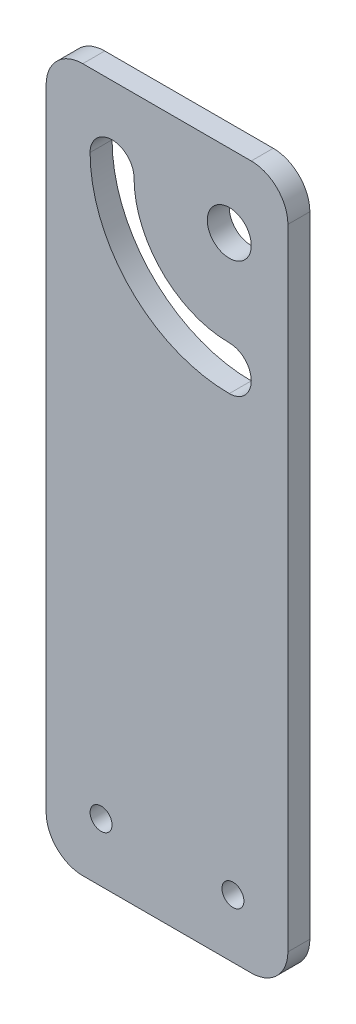
SolidWorks part; units mm, degrees
other "Marcação1"
sketch "Esboço5" plane through (0, 50, 68.25) normal (-0.797, 0.1637, 0.5813) x (0.5636, -0.1442, 0.8134)
material "Nylon - impressão"
ref_plane "Plano frontal" through (0, 0, 0) normal (0, 0, 1) x (1, 0, 0)
ref_plane "Plano superior" through (0, 0, 0) normal (0, 1, 0) x (1, 0, 0)
ref_plane "Plano direito" through (0, 0, 0) normal (1, 0, 0) x (0, 0, -1)
sketch "Esboço1" plane through (0, 0, 0) normal (0, 0, 1) x (1, 0, 0)
  line L1 (5, 50) -> (28, 50)
  line L4 (25, 40) -> (25, 37) construction
  line L6 (28, -46) -> (5, -46)
  line L8 (33, 45) -> (33, -41)
  line L9 (0, 45) -> (0, -41)
  line L10 (16.5, -46) -> (16.5, -17.8421) construction
  line L11 (0, 16.5) -> (33, 16.5) construction
  circle A0 centre (25, 40) radius 3
  arc A2 (25, 24) -> (9, 40) centre (25, 40) cw construction
  arc A3 (6, 40) -> (25, 21) centre (25, 40) ccw
  arc A4 (12, 40) -> (25, 27) centre (25, 40) ccw
  arc A5 (12, 40) -> (6, 40) centre (9, 40) ccw
  arc A6 (25, 21) -> (25, 27) centre (25, 24) ccw
  circle A7 centre (25.5, -38) radius 1.5
  circle A8 centre (7.5, -38) radius 1.5
  arc A9 (5, -46) -> (0, -41) centre (5, -41) cw
  arc A10 (0, 45) -> (5, 50) centre (5, 45) cw
  arc A11 (33, -41) -> (28, -46) centre (28, -41) cw
  arc A12 (28, 50) -> (33, 45) centre (28, 45) cw
  point P10 (13.6863, 28.6863)
  point P25 (0, 50)
  point P28 (33, -46)
  point P31 (33, 50)
  dimension "D3" = 6
  dimension "D5" = 16
  dimension "D6" = 13
  dimension "D2" = 3
  dimension "D4" = 8
  dimension "D8" = 7.5
  dimension "D9" = 5
  dimension "D1" = 96
  dimension "D7" = 33
  dimension "D10" = 67
extrude "Ressalto-extrusão2" add sketch "Esboço1" along normal blind 3
